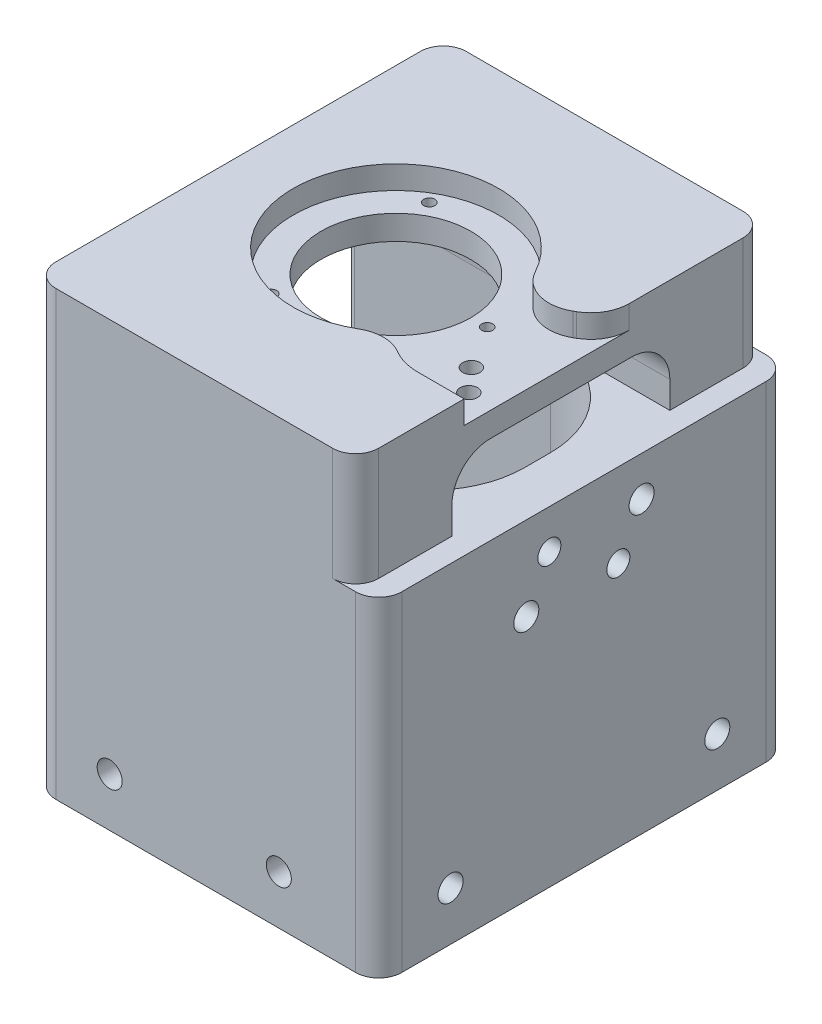
SolidWorks part; units mm, degrees
ref_plane "Front Plane" through (0, 0, 0) normal (0, 0, 1) x (1, 0, 0)
ref_plane "Top Plane" through (0, 0, 0) normal (0, 1, 0) x (1, 0, 0)
ref_plane "Right Plane" through (0, 0, 0) normal (1, 0, 0) x (0, 0, -1)
sketch "Sketch1" plane through (0, 0, 0) normal (0, 0, 1) x (1, 0, 0)
  line L0 (0, 0) -> (0, 83.75)
  line L1 (0, 83.75) -> (90, 83.75)
  line L2 (90, 83.75) -> (90, 0)
  line L3 (90, 0) -> (0, 0)
  dimension "D1" = 90
  dimension "D2" = 83.75
extrude "Boss-Extrude1" add sketch "Sketch1" along normal blind 106.8
sketch "Sketch2" plane through (0, 0, 0) normal (0, -1, 0) x (1, 0, 0)
  line L0 (0, 106.8) -> (90, 106.8)
  line L1 (90, 106.8) -> (90, 0)
  line L2 (90, 0) -> (0, 0)
  line L3 (0, 100.8) -> (84, 100.8)
  line L4 (84, 100.8) -> (84, 6)
  line L5 (84, 6) -> (0, 6)
  line L6 (0, 106.8) -> (0, 100.8)
  line L7 (0, 6) -> (0, 0)
  dimension "D1" = 6
extrude "Boss-Extrude2" add sketch "Sketch2" along normal blind 25.4
sketch "Sketch3" plane through (90, 0, 0) normal (1, 0, 0) x (0, 0, -1)
  line L0 (-6, -25.4) -> (-6, 0) construction
  line L1 (-100.8, -25.4) -> (-100.8, 0) construction
  line L2 (-6, -25.4) -> (-6, 0) construction
  line L3 (-100.8, -25.4) -> (-100.8, 0) construction
  circle A0 centre (-88.1, -12.7) radius 3.2575
  circle A1 centre (-18.7, -12.7) radius 3.2576
  point P4 (-100.8, -12.7)
  dimension "D1" = 12.7
  dimension "D3" = 6.5151
  dimension "D2" = 12.7
extrude "Cut-Extrude1" cut sketch "Sketch3" against normal through all both and the other way through all
sketch "Sketch4" plane through (0, 0, 0) normal (0, 0, -1) x (-1, 0, 0)
  line L0 (-84, -25.4) -> (-84, 0) construction
  line L1 (-84, -25.4) -> (-84, 0)
  line L2 (0, 83.75) -> (0, -25.4) construction
  circle A0 centre (-64, -12.7) radius 3.2576
  circle A1 centre (-20, -12.7) radius 3.2576
  point P6 (-84, -12.7)
  dimension "D1" = 6.5151
  dimension "D2" = 6.5151
  dimension "D3" = 20
  dimension "D4" = 20
extrude "Cut-Extrude2" cut sketch "Sketch4" against normal through all both and the other way through all contours A0 | A1
sketch "Sketch5" plane through (0, 0, 0) normal (-1, 0, 0) x (0, 0, 1)
  line L0 (25.05, 0) -> (25.05, 77.4)
  line L1 (100.8, 0) -> (6, 0) construction
  line L2 (25.05, 77.4) -> (81.75, 77.4)
  line L3 (81.75, 77.4) -> (81.75, 0)
  line L5 (6, -25.4) -> (6, 0) construction
  line L6 (100.8, -25.4) -> (100.8, 0) construction
  line L7 (106.8, 83.75) -> (0, 83.75) construction
  line L8 (25.05, 0) -> (81.75, 0)
  dimension "D1" = 19.05
  dimension "D2" = 19.05
  dimension "D3" = 6.35
extrude "Cut-Extrude3" cut sketch "Sketch5" against normal up to surface (84 mm away) up to face at (84, -12.7, 84.8424)
fillet "Fillet3" radius 10 2 edges at (42, 77.4, 81.75) (42, 77.4, 25.05)
sketch "Sketch6" plane through (0, 83.75, 0) normal (0, 1, 0) x (1, 0, 0)
  line L0 (90, -106.8) -> (90, 0) construction
  line L1 (84, -71.75) -> (84, -35.05) construction
  line L2 (84, -71.75) -> (84, -35.05)
  circle A0 centre (41.08, -53.4) radius 23.75 construction
  circle A1 centre (64.83, -53.4) radius 1.45
  circle A2 centre (29.205, -73.9681) radius 1.45
  circle A3 centre (29.205, -32.8319) radius 1.45
  circle A4 centre (41.08, -53.4) radius 19.5
  point P4 (90, -53.4)
  point P16 (76.2, -46.3969)
  dimension "D1" = 42.92
  dimension "D2" = 47.5
  dimension "D3" = 2.9
  dimension "D5" = 39
  dimension "D4" = 3
extrude "Cut-Extrude4" cut sketch "Sketch6" against normal through all both and the other way through all contours A3 | A4 | A1 | A2
sketch "Sketch7" plane through (90, 0, 0) normal (1, 0, 0) x (0, 0, -1)
  line L0 (-71.75, 77.4) -> (-35.05, 77.4) construction
  line L1 (-71.75, 77.4) -> (-35.05, 77.4)
  line L2 (-106.8, 60.4) -> (0, 60.4)
  line L3 (-106.8, -25.4) -> (-106.8, 83.75) construction
  line L4 (0, -25.4) -> (0, 83.75) construction
  line L5 (-71.75, 77.4) -> (-106.8, 77.4)
  line L6 (-106.8, 77.4) -> (-106.8, 60.4)
  line L7 (-35.05, 77.4) -> (0, 77.4)
  line L8 (0, 77.4) -> (0, 60.4)
  line M9 (0, -25.4) -> (0, 83.75)
  line M10 (0, 83.75) -> (-106.8, 83.75)
  line M11 (-106.8, 83.75) -> (-106.8, -25.4)
  dimension "D1" = 17
extrude "Cut-Extrude5" cut sketch "Sketch7" against normal up to surface (6 mm away) and the other way through all contours L1 L7 L5 M9 M10 M11 | L7 L1 L5 L2 M11 M9 up to face at (84, -12.7, 84.8424)
sketch "Sketch8" plane through (0, 83.75, 0) normal (0, 1, 0) x (1, 0, 0)
  line L4 (84, -106.8) -> (84, 0)
  line L5 (84, 0) -> (0, 0)
  line L6 (0, 0) -> (0, -106.8)
  line L7 (0, -106.8) -> (84, -106.8)
  line L8 (84, -106.8) -> (84, 0)
  line L9 (84, 0) -> (0, 0)
  line L10 (0, 0) -> (0, -106.8)
  line L11 (0, -106.8) -> (84, -106.8)
  circle A0 centre (41.08, -53.4) radius 26.75
  dimension "D1" = 53.5
  dimension "D2" = 0
extrude "Boss-Extrude3" add sketch "Sketch8" along normal blind 6
sketch "Sketch9" plane through (0, 77.4, 0) normal (0, -1, 0) x (1, 0, 0)
  circle A0 centre (29.205, 32.8319) radius 1.45 construction
  circle A1 centre (64.83, 53.4) radius 1.45 construction
  circle A2 centre (29.205, 73.9681) radius 1.45 construction
  circle A3 centre (29.205, 32.8319) radius 1.45 construction
  circle A4 centre (64.83, 53.4) radius 1.45 construction
  circle A5 centre (29.205, 73.9681) radius 1.45 construction
  circle A6 centre (29.205, 32.8319) radius 2.5
  circle A7 centre (29.205, 73.9681) radius 2.5
  circle A8 centre (64.83, 53.4) radius 2.5
  dimension "D1" = 5
extrude "Cut-Extrude6" cut sketch "Sketch9" along normal through all contours A6 | A7 | A8
sketch "Sketch10" plane through (90, 0, 0) normal (1, 0, 0) x (0, 0, -1)
  line L0 (-25.05, 0) -> (-6, 0) construction
  line L1 (-100.8, 0) -> (-81.75, 0) construction
  line L2 (-6, -25.4) -> (-6, 0) construction
  line L3 (-100.8, -25.4) -> (-100.8, 0) construction
  line L4 (-25.05, 0) -> (-6, 0)
  line L5 (-100.8, 0) -> (-81.75, 0)
  line L6 (-6, -25.4) -> (-6, 0)
  line L7 (-100.8, -25.4) -> (-100.8, 0)
  circle A0 centre (-68.4, 38.6) radius 3.2575
  circle A1 centre (-62.4, 50.2) radius 3
  circle A2 centre (-44.45, 38.6) radius 3
  circle A3 centre (-38.4, 50.07) radius 3.2576
  point P14 (-63.2311, 36.2809)
  point P15 (-62.4, 48.6953)
  point P16 (-38.4, 49.6307)
  point P17 (-42.3451, 38.6)
  point P18 (0, 0)
  dimension "D1" = 32.4
  dimension "D2" = 6.5151
  dimension "D6" = 6
  dimension "D3" = 38.6
  dimension "D4" = 38.4
  dimension "D5" = 50.2
  dimension "D7" = 30
  dimension "D8" = 11.47
  dimension "D9" = 23.95
extrude "Cut-Extrude7" cut sketch "Sketch10" against normal through all contours A1 | A0 | A3 | A2
sketch "Sketch11" plane through (84, 0, 0) normal (-1, 0, 0) x (0, 0, 1)
  line L1 (25.05, 0) -> (81.75, 0)
  line L2 (25.05, 0) -> (25.05, 60.4)
  line L3 (25.05, 60.4) -> (81.75, 60.4)
  line L4 (81.75, 0) -> (81.75, 60.4)
  circle A0 centre (68.4, 38.6) radius 3.2575 construction
  circle A1 centre (62.4, 50.2) radius 3 construction
  circle A2 centre (44.45, 38.6) radius 3 construction
  circle A3 centre (38.4, 50.07) radius 3.2575 construction
  circle A4 centre (68.4, 38.6) radius 3.2575
  circle A5 centre (62.4, 50.2) radius 3
  circle A6 centre (44.45, 38.6) radius 3
  circle A7 centre (38.4, 50.07) radius 3.2576
extrude "Boss-Extrude4" add sketch "Sketch11" along normal blind 6
fillet "Fillet5" radius 25 2 edges at (78, 30.2, 81.75) (78, 30.2, 25.05)
sketch "Sketch12" plane through (78, 0, 0) normal (-1, 0, 0) x (0, 0, 1)
  circle A0 centre (68.4, 38.6) radius 3.2576 construction
  circle A1 centre (38.4, 50.07) radius 3.2576 construction
  circle A2 centre (68.4, 38.6) radius 3.2576
  circle A3 centre (38.4, 50.07) radius 3.2576
  circle A4 centre (38.4, 50.07) radius 7
  circle A5 centre (68.4, 38.6) radius 7
  dimension "D1" = 14
extrude "Cut-Extrude8" cut sketch "Sketch12" along normal through all
sketch "Sketch13" plane through (0, 89.75, 0) normal (0, 1, 0) x (1, 0, 0)
  circle A0 centre (71.87, -64.56) radius 2.25
  circle A1 centre (77.19, -70.54) radius 2.25
  circle A2 centre (41.08, -53.4) radius 19.5 construction
  circle A3 centre (41.08, -53.4) radius 19.5 construction
  dimension "D1" = 11.16
  dimension "D5" = 4.5
  dimension "D2" = 30.79
  dimension "D3" = 17.14
  dimension "D4" = 36.11
extrude "Cut-Extrude9" cut sketch "Sketch13" against normal up to surface (12.35 mm away) up to face at (69.0644, 77.4, 53.4)
sketch "Sketch14" plane through (0, 89.75, 0) normal (0, 1, 0) x (1, 0, 0)
  line L0 (84, -78.56) -> (71.87, -78.56)
  line L1 (84, -106.8) -> (84, 0) construction
  line L2 (64.87, -52.4356) -> (84, -41.3909)
  circle A0 centre (71.87, -64.56) radius 14
  circle A1 centre (41.08, -53.4) radius 26.75 construction
  circle A2 centre (41.08, -53.4) radius 26.75
  circle M5 centre (71.87, -64.56) radius 2.25
  circle M6 centre (77.19, -70.54) radius 2.25
  line M8 (84, -106.8) -> (84, 0)
  circle M11 centre (41.08, -53.4) radius 26.75
  dimension "D1" = 30
  dimension "D2" = 14
extrude "Cut-Extrude10" cut sketch "Sketch14" against normal offset from surface (6 mm away) 6.35 contours A0 L0 L2 M8 M11 | A0 M11 M6 M5 | A0 L0 M8
fillet "Fillet6" radius 10 3 edges at (67.7033, 86.75, 50.7998) (60.1269, 86.75, 72.1824) (84, 86.75, 41.3909)
fillet "Fillet2" radius 6 6 edges at (0, 32.175, 106.8) (0, -25.4, 103.8) (0, -25.4, 3) (0, 32.175, 0) (90, 17.5, 0) (90, 17.5, 106.8)
sketch "Sketch15" plane through (0, 77.4, 0) normal (0, -1, 0) x (1, 0, 0)
  line L0 (71.87, 64.56) -> (77.19, 70.54) construction
  line L1 (68.5079, 67.551) -> (73.8279, 73.531)
  line L2 (75.2321, 61.569) -> (80.5521, 67.549)
  circle A0 centre (71.87, 64.56) radius 2.25 construction
  circle A1 centre (77.19, 70.54) radius 2.25 construction
  circle A2 centre (71.87, 64.56) radius 2.25
  circle A3 centre (77.19, 70.54) radius 2.25
  arc A4 (68.5079, 67.551) -> (75.2321, 61.569) centre (71.87, 64.56) ccw
  arc A5 (80.5521, 67.549) -> (73.8279, 73.531) centre (77.19, 70.54) ccw
  point P6 (74.53, 67.55)
  dimension "D1" = 4.5
extrude "Cut-Extrude11" cut sketch "Sketch15" against normal blind 3 and the other way blind 17
fillet "Fillet8" radius 2 5 edges at (0, 33.7, 81.75) (0, 77.4, 53.4) (0, 33.7, 25.05) (0, 74.4711, 78.8211) (0, 74.4711, 27.9789)
equation "\"D2@Sketch5\"=\"D1@Sketch5\""
